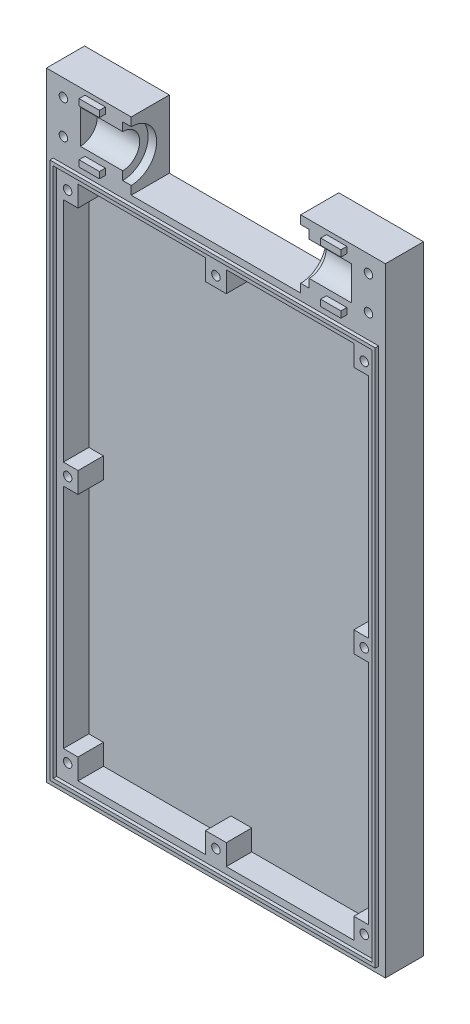
SolidWorks part; units mm, degrees
ref_plane "Ön Düzlem" through (0, 0, 0) normal (0, 0, 1) x (1, 0, 0)
ref_plane "Üst Düzlem" through (0, 0, 0) normal (0, 1, 0) x (1, 0, 0)
ref_plane "Sağ Düzlem" through (0, 0, 0) normal (1, 0, 0) x (0, 0, -1)
sketch "Çizim1" plane through (0, 0, 0) normal (0, 0, 1) x (1, 0, 0)
  line L0 (-33.0511, 79.7147) -> (-53.0511, 79.7147)
  line L1 (-53.0511, 79.7147) -> (-53.0511, 63.7147)
  line L2 (6.9489, 79.7147) -> (6.9489, 63.7147)
  line L3 (26.9489, 63.7147) -> (26.9489, 79.7147)
  line L4 (26.9489, 79.7147) -> (6.9489, 79.7147)
  line L5 (-53.0511, 63.7147) -> (26.9489, 63.7147)
  line L6 (-53.0511, 63.7147) -> (-53.0511, -66.2853)
  line L7 (-53.0511, -66.2853) -> (26.9489, -66.2853)
  line L8 (26.9489, -66.2853) -> (26.9489, 63.7147)
  line L9 (-33.0511, 79.7147) -> (-33.0511, 63.7147)
  line L10 (-51.4511, 62.1147) -> (-51.4511, -64.6853)
  line L11 (-51.4511, -64.6853) -> (25.3489, -64.6853)
  line L12 (25.3489, -64.6853) -> (25.3489, 62.1147)
  line L13 (-51.4511, 62.1147) -> (25.3489, 62.1147)
  line L14 (-50.6511, 61.3147) -> (24.5489, 61.3147)
  line L15 (24.5489, -63.8853) -> (24.5489, 61.3147)
  line L16 (-50.6511, -63.8853) -> (24.5489, -63.8853)
  line L17 (-50.6511, 61.3147) -> (-50.6511, -63.8853)
  line L18 (-45.6011, 54.8147) -> (-45.6011, 59.7147)
  line L19 (-45.6011, 59.7147) -> (-15.5011, 59.7147)
  line L20 (-15.5011, 59.7147) -> (-15.5011, 54.8147)
  line L21 (-15.5011, 54.8147) -> (-10.6011, 54.8147)
  line L22 (-10.6011, 54.8147) -> (-10.6011, 59.7147)
  line L23 (-10.6011, 59.7147) -> (19.4989, 59.7147)
  line L24 (19.4989, 59.7147) -> (19.4989, 54.8147)
  line L25 (19.4989, 54.8147) -> (22.9489, 54.8147)
  line L26 (22.9489, 54.8147) -> (22.9489, 1.1647)
  line L27 (22.9489, 1.1647) -> (19.4989, 1.1647)
  line L28 (19.4989, 1.1647) -> (19.4989, -3.7353)
  line L29 (19.4989, -3.7353) -> (22.9489, -3.767)
  line L30 (22.9489, -3.767) -> (22.9489, -57.3853)
  line L31 (22.9489, -57.3853) -> (19.4989, -57.3853)
  line L32 (19.4989, -57.3853) -> (19.4989, -62.2853)
  line L33 (19.4989, -62.2853) -> (-10.6011, -62.2853)
  line L34 (-10.6011, -62.2853) -> (-10.6011, -57.3853)
  line L35 (-10.6011, -57.3853) -> (-15.5011, -57.3853)
  line L36 (-15.5011, -57.3853) -> (-15.5011, -62.2853)
  line L37 (-15.5011, -62.2853) -> (-45.6011, -62.2853)
  line L38 (-45.6011, -62.2853) -> (-45.6011, -57.3853)
  line L39 (-45.6011, -57.3853) -> (-49.0511, -57.3853)
  line L40 (-49.0511, -57.3853) -> (-49.0511, -3.7353)
  line L41 (-49.0511, -3.7353) -> (-45.6011, -3.7353)
  line L42 (-45.6011, -3.7353) -> (-45.6011, 1.1647)
  line L43 (-45.6011, 1.1647) -> (-49.0511, 1.1647)
  line L44 (-49.0511, 1.1647) -> (-49.0511, 54.8147)
  line L45 (-49.0511, 54.8147) -> (-45.6011, 54.8147)
  line L46 (13.0489, 66.2147) -> (13.0489, 64.7147)
  line L47 (13.0489, 64.7147) -> (17.8489, 64.7147)
  line L48 (17.8489, 66.2147) -> (17.8489, 64.7147)
  line L49 (13.0489, 66.2147) -> (17.8489, 66.2147)
  line L50 (13.0489, 78.7147) -> (13.0489, 77.2147)
  line L51 (13.0489, 77.2147) -> (17.8489, 77.2147)
  line L52 (17.8489, 78.7147) -> (17.8489, 77.2147)
  line L53 (13.0489, 78.7147) -> (17.8489, 78.7147)
  line L54 (-43.9511, 78.7147) -> (-43.9511, 77.2147)
  line L55 (-43.9511, 77.2147) -> (-39.1511, 77.2147)
  line L56 (-39.1511, 78.7147) -> (-39.1511, 77.2147)
  line L57 (-43.9511, 78.7147) -> (-39.1511, 78.7147)
  line L58 (-43.9511, 66.2147) -> (-43.9511, 64.7147)
  line L59 (-43.9511, 64.7147) -> (-39.1511, 64.7147)
  line L60 (-39.1511, 66.2147) -> (-39.1511, 64.7147)
  line L61 (-43.9511, 66.2147) -> (-39.1511, 66.2147)
  circle A0 centre (-48.0511, 57.2647) radius 1
  circle A1 centre (-49.0511, 67.7147) radius 1
  circle A2 centre (-49.0511, 75.7147) radius 1
  circle A3 centre (22.9489, 75.7147) radius 1
  circle A4 centre (22.9489, 67.7147) radius 1
  circle A5 centre (21.9489, 57.2647) radius 1
  circle A6 centre (-13.0511, 57.2647) radius 1
  circle A7 centre (21.9489, -1.2853) radius 1
  circle A8 centre (21.9489, -59.8353) radius 1
  circle A9 centre (-13.0511, -59.8353) radius 1
  circle A10 centre (-48.0511, -59.8353) radius 1
  circle A11 centre (-48.0511, -1.2853) radius 1
extrude "Yükseklik-Ekstrüzyon1" add sketch "Çizim1" along normal blind 9 contours L14 L17 L16 L15 A11 A10 A9 A8 A7 A6 A5 A0 L44 L45 L18 L19 L20 L21 L22 L23 L24 L25 L26 L27 L28 L29 L30 L31 L32 L33 L34 L35 L36 L37 L38 L39 L40 L41 L42 L43 | L7 L8 L5 L6 L10 L13 L12 L11 | L2 L5 L3 L4 A4 A3 L46 L49 L48 L47 L50 L53 L52 L51 | L9 L0 L1 L5 A2 A1 L54 L57 L56 L55 L58 L61 L60 L59 region at (-42.9973, 71.7147, 0) region at (-13.0511, 62.1883, 0) region at (16.8951, 71.7147, 0) region at (-13.0511, 59.8542, 0)
extrude "Yükseklik-Ekstrüzyon2" add sketch "Çizim1<3>" along normal blind 10.4 contours L57 L54 L55 L56 | L61 L58 L59 L60 | L49 L46 L47 L48 | L53 L50 L51 L52 region at (15.4489, 65.4647, 0) region at (15.4489, 77.9647, 0) region at (-41.5511, 77.9647, 0) region at (-41.5511, 65.4647, 0)
sketch "Çizim1<3>" plane through (0, 0, 0) normal (0, 0, 1) x (1, 0, 0) same geometry as "Çizim1"
extrude "Yükseklik-Ekstrüzyon3" add sketch "Çizim1<4>" along normal blind 9.8 contours L13 L10 L11 L12 L17 L14 L15 L16 region at (-13.0511, 61.9665, 0)
sketch "Çizim1<4>" plane through (0, 0, 0) normal (0, 0, 1) x (1, 0, 0) same geometry as "Çizim1"
extrude "Yükseklik-Ekstrüzyon4" add sketch "Çizim1<5>" along normal blind 3 contours L45 L44 L43 L42 L41 L40 L39 L38 L37 L36 L35 L34 L33 L32 L31 L30 L29 L28 L27 L26 L25 L24 L23 L22 L21 L20 L19 L18 region at (-13.0513, -1.2853, 0)
sketch "Çizim1<5>" plane through (0, 0, 0) normal (0, 0, 1) x (1, 0, 0) same geometry as "Çizim1"
sketch "Çizim2" plane through (6.9489, 0, 0) normal (-1, 0, 0) x (0, 0, 1)
  line L0 (9, 79.7147) -> (9, 63.7147) construction
  line L1 (9, 77.7147) -> (9, 65.7147)
  arc A0 (9, 75.7147) -> (9, 67.7147) centre (9, 71.7147) ccw
  arc A1 (9, 77.7147) -> (9, 65.7147) centre (9, 71.7147) ccw
  line M3 (9, 63.7147) -> (9, 79.7147)
extrude "Kes-Ekstrüzyon1" cut sketch "Çizim2" against normal blind 12 and the other way blind 52 contours L1 A0 region at (6.9489, 71.7147, 7.3023)
extrude "Kes-Ekstrüzyon2" cut sketch "Çizim2<3>" against normal blind 2 and the other way blind 42 contours A1 A0 M3 region at (6.9489, 76.7147, 8.8658)
sketch "Çizim2<3>" plane through (6.9489, 0, 0) normal (-1, 0, 0) x (0, 0, 1) same geometry as "Çizim2"
